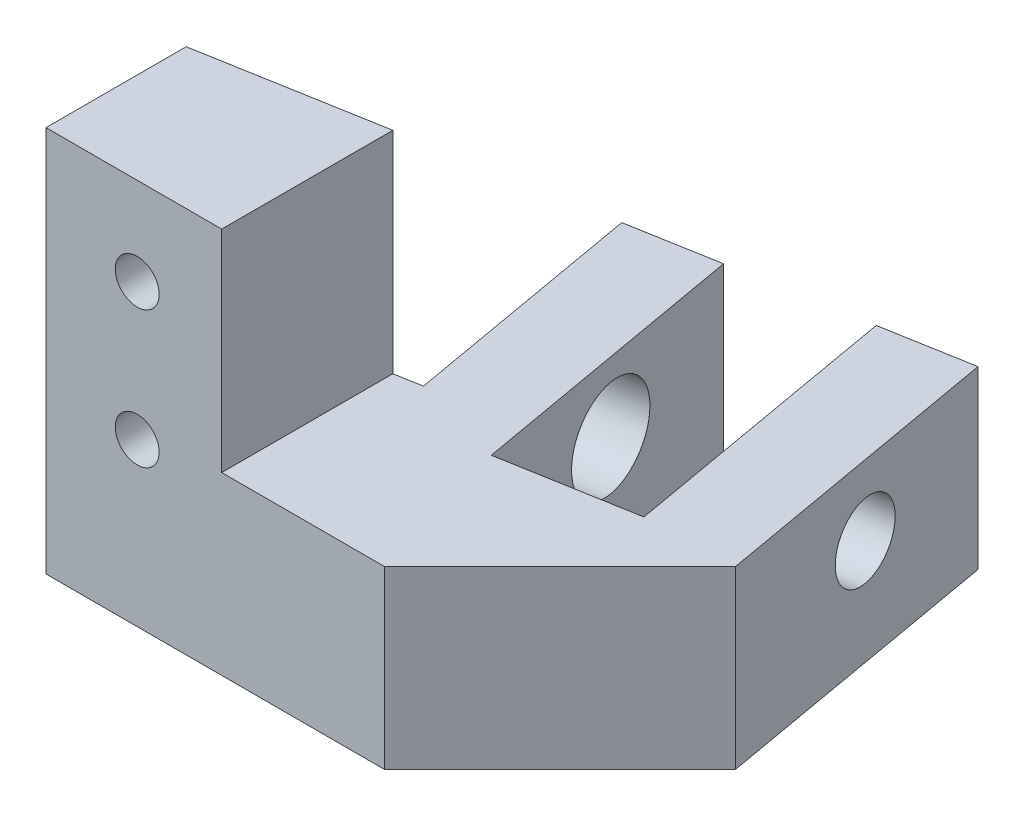
SolidWorks part; units mm, degrees
ref_plane "Plan de face" through (0, 0, 0) normal (0, 0, 1) x (1, 0, 0)
ref_plane "Plan de dessus" through (0, 0, 0) normal (0, 1, 0) x (1, 0, 0)
ref_plane "Plan de droite" through (0, 0, 0) normal (1, 0, 0) x (0, 0, -1)
sketch "Esquisse1" plane through (0, 0, 0) normal (0, 0, 1) x (1, 0, 0)
  line L0 (0, 0) -> (29.25, 0)
  line L1 (29.25, 0) -> (29.25, 10)
  line L2 (29.25, 10) -> (10, 10)
  line L3 (10, 10) -> (10, 22)
  line L4 (10, 22) -> (0, 22)
  line L5 (0, 22) -> (0, 0)
  dimension "D1" = 10
  dimension "D2" = 22
  dimension "D3" = 10
  dimension "D4" = 19.25
extrude "Boss.-Extru.1" add sketch "Esquisse1" along normal blind 10
sketch "Esquisse2" plane through (0, 10, 0) normal (0, 1, 0) x (1, 0, 0)
  line L0 (29.25, 0) -> (26.298, 16.7417)
  line L1 (26.298, 16.7417) -> (21.3739, 15.8735)
  line L2 (21.3739, 15.8735) -> (24.1729, 0)
  line L3 (29.25, 0) -> (10, 0) construction
  line L4 (24.1729, 0) -> (29.25, 0)
  line L5 (16.5572, 0) -> (13.9879, 14.5711)
  line L6 (13.9879, 14.5711) -> (9.0638, 13.7029)
  line L7 (9.0638, 13.7029) -> (11.48, 0)
  line L8 (16.5572, 0) -> (11.48, 0)
  line L9 (29.25, -10) -> (29.25, 0) construction
  dimension "D1" = 5
  dimension "D2" = 7.5
  dimension "D3" = 190
  dimension "D4" = 17
extrude "Boss.-Extru.2" add sketch "Esquisse2" against normal up to surface (10 mm away) up to face at (14.625, 0, 5)
sketch "Esquisse3" plane through (0, 10, 0) normal (0, 1, 0) x (1, 0, 0)
  line L0 (16.5572, 0) -> (16.8176, -1.4772)
  line L1 (16.8176, -1.4772) -> (24.2037, -0.1749)
  line L2 (24.2037, -0.1749) -> (24.1729, 0)
  line L3 (21.3739, 15.8735) -> (24.1729, 0) construction
  line L4 (16.5572, 0) -> (13.9879, 14.5711) construction
  line L5 (24.1729, 0) -> (16.5572, 0)
  dimension "D1" = 1.5
extrude "Enlèv. mat.-Extru.1" cut sketch "Esquisse3" against normal up to next
sketch "Esquisse4" plane through (11.1339, 0, -1.9632) normal (-0.9848, 0, 0.1736) x (0.1736, 0, 0.9848)
  line L0 (-11.9208, 10) -> (1.9935, 10) construction
  line L1 (1.9935, 0) -> (1.9935, 10) construction
  circle A0 centre (-4.0065, 6) radius 2.75
  dimension "D2" = 5.5
  dimension "D1" = 4
  dimension "D3" = 6
extrude "Enlèv. mat.-Extru.2" cut sketch "Esquisse4" against normal up to next
sketch "Esquisse5" plane through (23.444, 0, -4.1338) normal (-0.9848, 0, 0.1736) x (0.1736, 0, 0.9848)
  circle A0 centre (-4.0065, 6) radius 2.1
  circle A1 centre (-4.0065, 6) radius 2.75 construction
  circle A2 centre (-4.0065, 6) radius 2.75 construction
  dimension "D1" = 4.2
extrude "Enlèv. mat.-Extru.3" cut sketch "Esquisse5" against normal up to next
chamfer "Chanfrein1" distance 10 angle 45 1 edges at (29.25, 5, 10)
sketch "Esquisse6" plane through (0, 22, 0) normal (0, 1, 0) x (1, 0, 0)
  line L0 (0, 0) -> (11.48, 0)
  line L1 (11.48, 0) -> (0, -2.0242)
  line L2 (0, -10) -> (0, 0) construction
  line L3 (0, -2.0242) -> (0, 0)
  line L4 (9.0638, 13.7029) -> (11.48, 0) construction
extrude "Enlèv. mat.-Extru.4" cut sketch "Esquisse6" against normal up to next
sketch "Esquisse7" plane through (0, 0, 10) normal (0, 0, 1) x (1, 0, 0)
  line L0 (0, 22) -> (0, 0) construction
  line L1 (10, 22) -> (0, 22) construction
  circle A0 centre (5.19, 17) radius 1.25
  circle A1 centre (5.19, 9.22) radius 1.25
  dimension "D1" = 2.5
  dimension "D2" = 5.19
  dimension "D3" = 5
  dimension "D4" = 7.78
extrude "Enlèv. mat.-Extru.5" cut sketch "Esquisse7" against normal up to next
